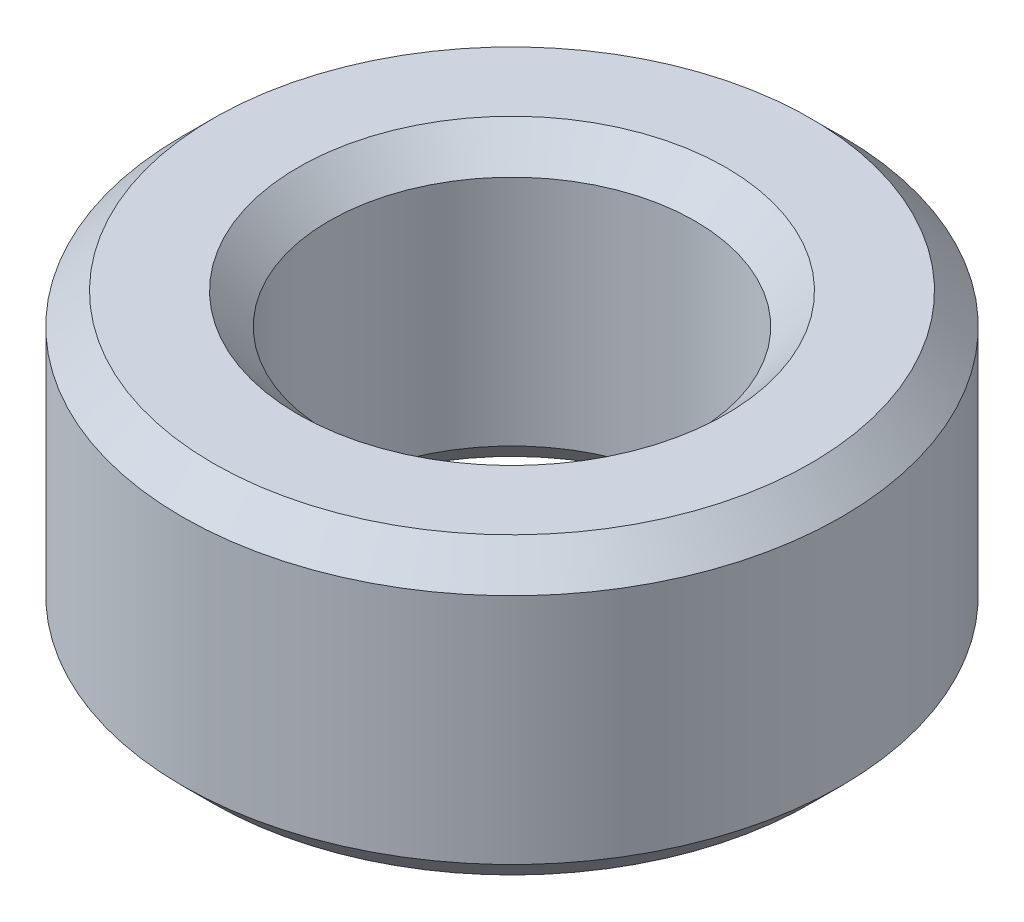
SolidWorks part; units mm, degrees
ref_plane "Front Plane" through (0, 0, 0) normal (0, 0, 1) x (1, 0, 0)
ref_plane "Top Plane" through (0, 0, 0) normal (0, 1, 0) x (1, 0, 0)
ref_plane "Right Plane" through (0, 0, 0) normal (1, 0, 0) x (0, 0, -1)
sketch "Sketch1" plane through (0, 0, 0) normal (0, 1, 0) x (1, 0, 0)
  circle A0 centre (0, 0) radius 27.5
  dimension "SLEEVE_OD" = 55
extrude "Boss-Extrude1" add sketch "Sketch1" along normal blind 24.5736
sketch "Sketch2" plane through (0, 0, 0) normal (0, 1, 0) x (1, 0, 0)
  circle A0 centre (0, 0) radius 15.2622
  dimension "BORE_D" = 30.5243
extrude "Cut-Extrude1" cut sketch "Sketch2" along normal through all
chamfer "Chamfer1" distance 2.5792 angle 45 4 edges at (0, 24.5736, 15.2622) (0, 0, 15.2622) (0, 0, 27.5) (0, 24.5736, 27.5)
